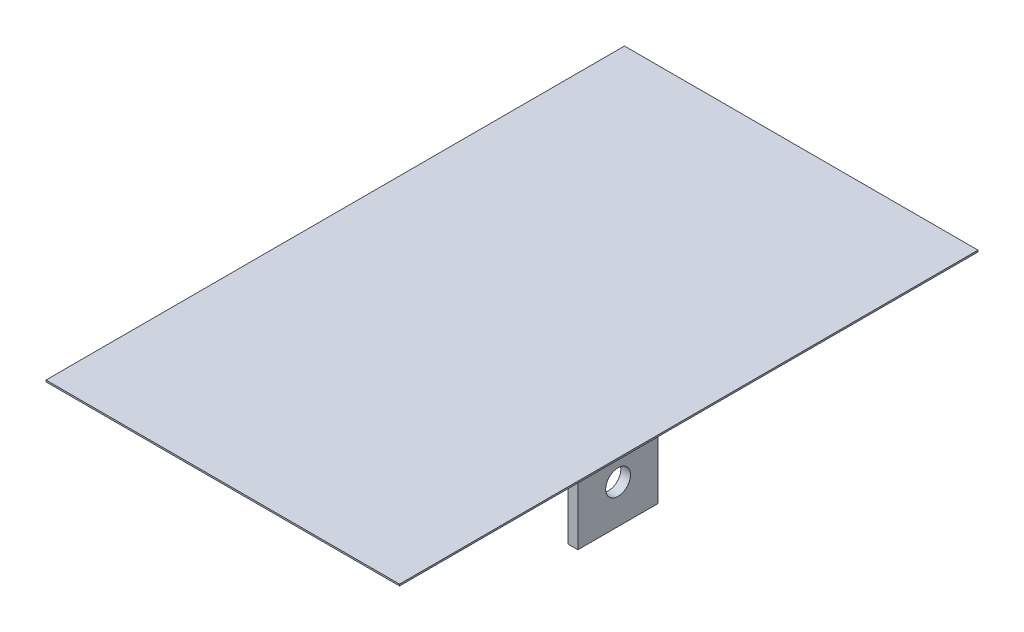
SolidWorks part; units mm, degrees
note: The reader was unsure of these and kept them because the rebuilt part matched: shared geometry of "Sketch1<3>".
ref_plane "Front Plane" through (0, 0, 0) normal (0, 0, 1) x (1, 0, 0)
ref_plane "Top Plane" through (0, 0, 0) normal (0, 1, 0) x (1, 0, 0)
ref_plane "Right Plane" through (0, 0, 0) normal (1, 0, 0) x (0, 0, -1)
sketch "Sketch1" plane through (0, 0, 0) normal (0, 1, 0) x (1, 0, 0)
  line L0 (-78.0423, 49.8707) -> (-78.0423, -130.1293) construction
  line L1 (-133.0423, 49.8707) -> (-23.0423, 49.8707)
  line L2 (-133.0423, 49.8707) -> (-133.0423, -130.1293)
  line L3 (-133.0423, -130.1293) -> (-23.0423, -130.1293)
  line L4 (-23.0423, 49.8707) -> (-23.0423, -130.1293)
  line L6 (-108.0423, -27.6293) -> (-111.0423, -27.6293)
  line L7 (-108.0423, -27.6293) -> (-108.0423, -52.6293)
  line L9 (-111.0423, -27.6293) -> (-111.0423, -52.6293)
  line L13 (-133.0423, -40.1293) -> (-23.0423, -40.1293) construction
  line L22 (-108.0423, -52.6293) -> (-111.0423, -52.6293)
  line L23 (-108.0423, -40.1293) -> (-111.0423, -40.1293) construction
  line L24 (-48.0423, -52.6293) -> (-45.0423, -52.6293)
  line L25 (-45.0423, -27.6293) -> (-45.0423, -52.6293)
  line L26 (-48.0423, -27.6293) -> (-45.0423, -27.6293)
  line L27 (-48.0423, -27.6293) -> (-48.0423, -52.6293)
  dimension "D1" = 180
  dimension "D2" = 110
  dimension "D3" = 25
  dimension "D4" = 3
  dimension "D5" = 30
extrude "Boss-Extrude1" add sketch "Sketch1" along normal blind 0.5
extrude "Boss-Extrude2" add sketch "Sketch1<3>" against normal blind 40
sketch "Sketch1<3>" plane through (0, 0, 0) normal (0, 1, 0) x (1, 0, 0) same geometry as "Sketch1"
sketch "Sketch2" plane through (0, 0, 0) normal (0, 1, 0) x (1, 0, 0)
  line L0 (-78.0423, 49.8707) -> (-78.0423, -130.1293) construction
  line L1 (-133.0423, 49.8707) -> (-23.0423, 49.8707) construction
  line L2 (-133.0423, -130.1293) -> (-23.0423, -130.1293) construction
  line L3 (-23.0423, -40.1293) -> (-133.0423, -40.1293) construction
  line L4 (-23.0423, 49.8707) -> (-23.0423, -130.1293) construction
  line L5 (-133.0423, 49.8707) -> (-133.0423, -130.1293) construction
sketch "Sketch3" plane through (-108.0423, 0, 0) normal (1, 0, 0) x (0, 0, -1)
  line L0 (-27.6293, -40) -> (-52.6293, -40) construction
  line L1 (-40.1293, 0) -> (-40.1293, -40) construction
  line L2 (-27.6293, 0) -> (-52.6293, 0) construction
  circle A0 centre (-40.1293, -28) radius 10.6
  dimension "D1" = 21.2
  dimension "D2" = 12
extrude "Cut-Extrude1" cut sketch "Sketch3" against normal blind 1
sketch "Sketch4" plane through (-48.0423, 0, 0) normal (-1, 0, 0) x (0, 0, 1)
  line L0 (27.6293, -40) -> (52.6293, -40) construction
  line L1 (40.1293, -40) -> (40.1293, 0) construction
  circle A0 centre (40.1293, -28) radius 3.85
  dimension "D1" = 7.7
  dimension "D2" = 12
extrude "Cut-Extrude2" cut sketch "Sketch4" against normal through all
